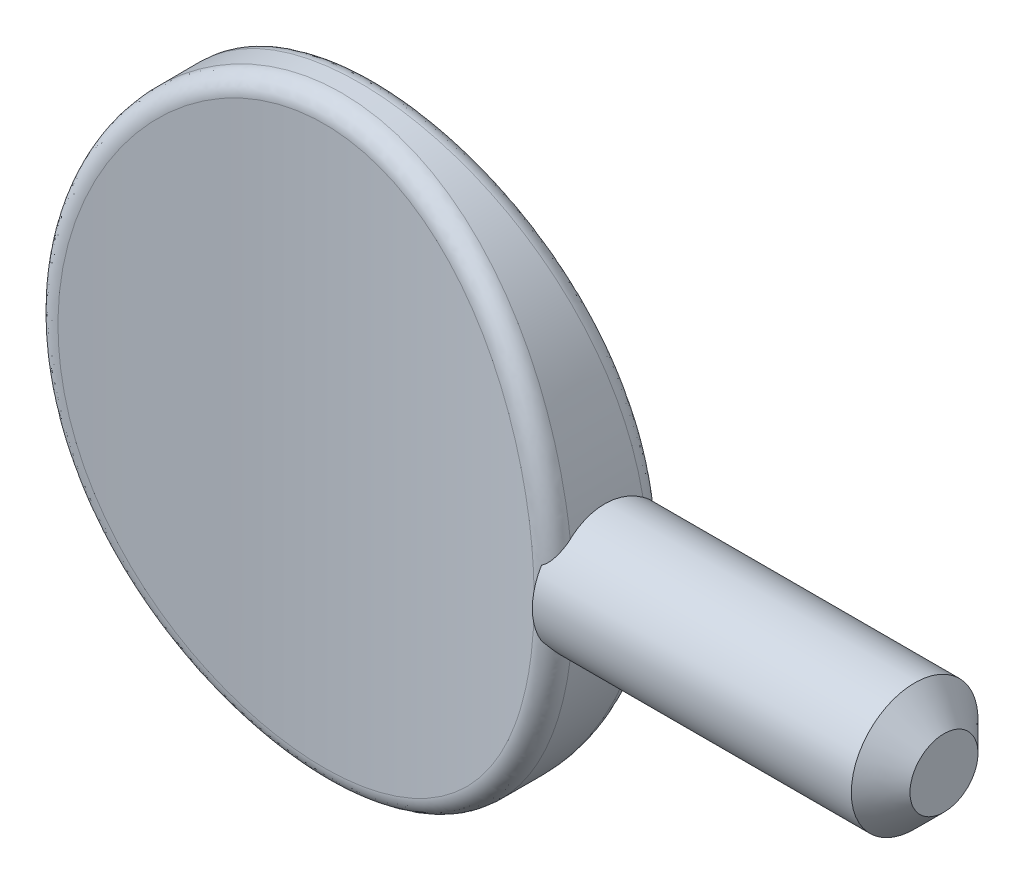
SolidWorks part; units mm, degrees
ref_plane "Front" through (0, 0, 0) normal (0, 0, 1) x (1, 0, 0)
ref_plane "Top" through (0, 0, 0) normal (0, 1, 0) x (1, 0, 0)
ref_plane "Right" through (0, 0, 0) normal (1, 0, 0) x (0, 0, -1)
ref_axis "Axis1" through (-50, 0, 0) along (1, 0, 0)
sketch "Sketch1" plane through (0, 0, 0) normal (0, 0, 1) x (1, 0, 0)
  line L0 (0, 0) -> (22.606, 0) construction
  line L1 (13.208, -2.413) -> (13.208, 2.413)
  line L2 (13.208, -2.413) -> (9.6776, -2.413) construction
  ellipse E0 centre (0, 0) end of major axis (0, -11.303) minor radius 9.906
  dimension "D2" = 3.302
  dimension "B" = 19.812
  dimension "L" = 12.7
extrude "Extrude1" add sketch "Sketch1" along normal mid plane 4.572
sketch "Sketch2" plane through (0, 0, 0) normal (0, 1, 0) x (1, 0, 0)
  line L0 (9.906, 2.286) -> (-9.906, 2.286) construction
  line L1 (0, 0) -> (0, 1.1721) construction
  line L2 (-1.7991, 0) -> (2.0444, 0) construction
  line L3 (-9.906, -2.286) -> (9.906, -2.286) construction
  line L6 (-9.906, 2.286) -> (-9.906, -2.286)
  line L7 (9.906, 2.286) -> (9.906, -2.286)
  arc A0 (-9.906, 2.286) -> (9.906, 2.286) centre (0, 40.2844) ccw
  arc A1 (-9.906, -2.286) -> (9.906, -2.286) centre (0, -40.2844) cw
extrude "Cut-Extrude1" cut sketch "Sketch2" against normal through all and the other way through all flip side to cut
fillet "Fillet3" radius 0.6773 2 edges at (-9.9037, -0.2444, 2.2854) (0.1692, 11.3014, -1.0164)
sketch "Sketch3" plane through (0, 0, 0) normal (0, 1, 0) x (1, 0, 0)
  line L0 (22.606, 0) -> (22.606, 1.2954)
  line L1 (0, 0) -> (21.0288, 0) construction
  line L2 (0, 0) -> (22.606, 0) construction
  line L3 (13.208, 2.413) -> (13.208, 0) construction
  line L4 (13.208, 2.413) -> (21.4884, 2.413)
  line L5 (22.606, 1.2954) -> (21.4884, 2.413)
  line L6 (13.208, 2.413) -> (9.3367, 2.413)
  line L7 (9.0722, 2.0783) -> (9.0722, 0)
  line L8 (9.3367, 0) -> (9.3367, 2.413) construction
  line L9 (9.0722, 0) -> (22.606, 0)
  arc A0 (9.3367, 2.413) -> (9.0722, 2.0783) centre (8.9927, 2.413) cw
  arc A3 (-9.906, 2.286) -> (9.906, 2.286) centre (0, 40.2844) ccw construction
  dimension "D1" = 45
revolve "Revolve1" add sketch "Sketch3" angle 360 about L0
cosmetic thread "Cosmetic Thread1" [suppressed]
sketch "Sketch4" plane through (0, 0, 0) normal (0, 0, 1) x (1, 0, 0)
  line L0 (0, 0) -> (27.7993, 0) construction
  line L1 (21.3051, 2.413) -> (21.4884, 2.0955)
  line L2 (21.4884, 2.0955) -> (21.6717, 2.413)
  line L3 (21.6717, 2.413) -> (21.6717, 2.7796)
  line L4 (21.6717, 2.7796) -> (21.3051, 2.7796)
  line L5 (21.3051, 2.7796) -> (21.3051, 2.413)
  line L6 (21.4884, 2.413) -> (21.4884, -2.413) construction
  dimension "D1" = 4.191
  dimension "D2" = 4.826
revolve "Cut-Revolve10" [suppressed] cut sketch "Sketch4" angle 360 about L0
pattern_linear "LPattern10" [suppressed] count 23 along (-1, 0, 0) of bodies 109
equation "\"D2@Sketch1\" = \"B@Sketch1\" / 6"
equation "\"D1@Fillet3\" = \"C1@Sketch2\" / 3"
equation "\"DIA@Sketch3\" = \"D@Sketch1\""
equation "\"D1@Cosmetic Thread1\" = \"L@Sketch1\" -  ( \"D@Sketch1\" - \"flat_dia@Sketch3\" )  / 2"
equation "\"D1@Sketch4\" = \"D2@Cosmetic Thread1\""
equation "\"D2@Sketch4\" = \"DIA@Sketch3\""
equation "\"D1@LPattern10\" = \"D1@Cosmetic Thread1\" / \"P@LPattern10\" "
